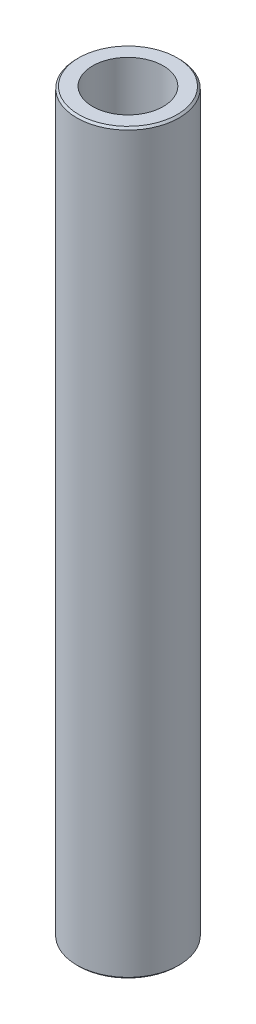
SolidWorks part; units mm, degrees
ref_plane "Front Plane" through (0, 0, 0) normal (0, 0, 1) x (1, 0, 0)
ref_plane "Top Plane" through (0, 0, 0) normal (0, 1, 0) x (1, 0, 0)
ref_plane "Right Plane" through (0, 0, 0) normal (1, 0, 0) x (0, 0, -1)
sketch "Sketch1" plane through (0, 0, 0) normal (0, 1, 0) x (1, 0, 0)
  circle A0 centre (0, 0) radius 22.5
  dimension "SHAFT_OD" = 45
extrude "Boss-Extrude1" add sketch "Sketch1" along normal blind 324.5583
sketch "Sketch2" plane through (0, 0, 0) normal (0, 1, 0) x (1, 0, 0)
  circle A0 centre (0, 0) radius 15.5346
  dimension "BORE_D" = 31.0693
extrude "Cut-Extrude1" cut sketch "Sketch2" along normal through all
chamfer "Chamfer1" distance 0.853 angle 45 2 edges at (0, 324.5583, 22.5) (0, 0, 22.5)
